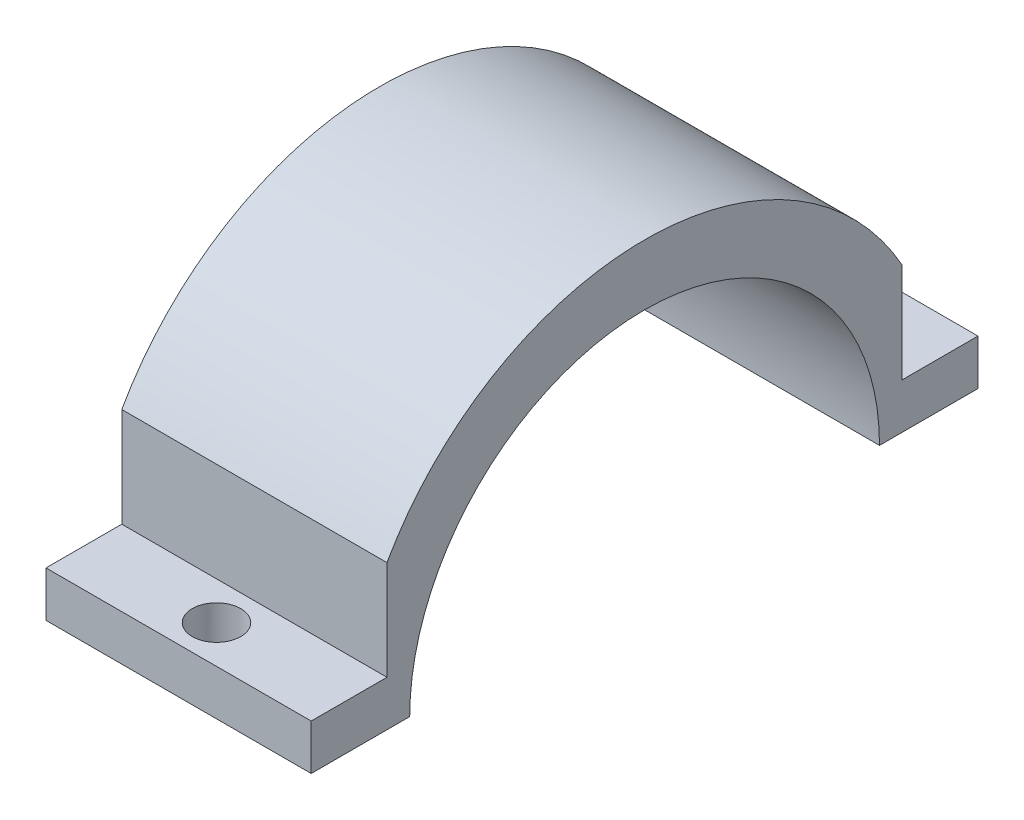
SolidWorks part; units mm, degrees
ref_plane "前视基准面" through (0, 0, 0) normal (0, 0, 1) x (1, 0, 0)
ref_plane "上视基准面" through (0, 0, 0) normal (0, 1, 0) x (1, 0, 0)
ref_plane "右视基准面" through (0, 0, 0) normal (1, 0, 0) x (0, 0, -1)
sketch "草图1" plane through (0, 0, 0) normal (0, 1, 0) x (1, 0, 0)
  line L1 (0, 0) -> (17, 0)
  line L2 (0, 0) -> (0, -40)
  line L3 (0, -40) -> (17, -40)
  line L4 (17, 0) -> (17, -40)
  dimension "D1" = 17
  dimension "D2" = 40
extrude "凸台-拉伸1" add sketch "草图1" along normal blind 50
sketch "草图2" plane through (0, 0, 0) normal (0, -1, 0) x (1, 0, 0)
  line L0 (0, 39) -> (0, 40)
  line L1 (-0.5, 39) -> (17, 39) construction
  line L2 (0, 0) -> (0, 40) construction
  line L3 (0, 40) -> (17, 40)
  line L4 (17, 40) -> (17, 39)
  line L5 (17, 40) -> (17, 0) construction
  line L6 (17, 39) -> (0, 39)
extrude "切除-拉伸1" cut sketch "草图2" against normal through all
sketch "草图4" plane through (0, 0, 0) normal (0, -1, 0) x (1, 0, 0)
  line L2 (-0.5, 0) -> (0, 0)
  line L3 (0, 0) -> (0, 39)
  line L4 (-0.5, 0) -> (-0.5, 39)
  line L5 (-0.5, 39) -> (0, 39)
extrude "凸台-拉伸2" add sketch "草图4" against normal up to vertex (50 mm away) up to point (0, 50, 39)
sketch "草图5" plane through (17, 0, 0) normal (1, 0, 0) x (0, 0, -1)
  circle A0 centre (-22, 4.5) radius 15.5
extrude "切除-拉伸2" cut sketch "草图5" against normal up to vertex (17.5 mm away) up to point (-0.5, 0, 0)
sketch "草图6" plane through (17, 0, 0) normal (1, 0, 0) x (0, 0, -1)
  line L0 (0, 24) -> (0, 3)
  line L2 (-22, 24) -> (-5, 24)
  line L3 (0, 50) -> (0, 0) construction
  line L4 (0, 24) -> (0, 50)
  line L5 (0, 50) -> (-39, 50)
  line L6 (-39, 50) -> (-39, 24)
  line L7 (-39, 50) -> (-39, 0) construction
  line L8 (-39, 24) -> (-22, 24)
  line L9 (0, 0) -> (0, 3)
  line L10 (0, 3) -> (-5, 3)
  line L11 (-5, 3) -> (-5, 24)
  line L12 (0, 24) -> (0, 3)
  line M11 (0, 0) -> (0, 50)
  line M12 (0, 50) -> (-39, 50)
  line M13 (-39, 50) -> (-39, 0)
extrude "切除-拉伸3" cut sketch "草图6" against normal up to vertex (17.5 mm away) contours L11 L10 L8 L2 M11 M12 M13 region at (17, 34.7949, 17.9048) up to point (-0.5, 0, 0)
sketch "草图7" plane through (0, 3, 0) normal (0, 1, 0) x (1, 0, 0)
  line L0 (8.25, -5) -> (8.25, 0)
  line L1 (-0.5, -5) -> (17, -5) construction
  line L2 (-0.5, 0) -> (17, 0) construction
  circle A0 centre (8.25, -2.5) radius 1.6
extrude "切除-拉伸4" cut sketch "草图7" against normal up to vertex (3 mm away) contours L0 A0 | L0 A0 region at (7.5709, 3, 2.5) region at (8.9291, 3, 2.5) up to point (17, 0, 0)
sketch "草图8" plane through (-0.5, 0, 0) normal (-1, 0, 0) x (0, 0, 1)
  line L0 (22, 4.5) -> (5, 4.5)
  line L1 (5, 3) -> (5, 24) construction
  line L2 (22, 4.5) -> (39, 4.5)
  line L3 (39, 24) -> (39, 0) construction
  line L4 (39, 4.5) -> (39, 0)
  line L5 (39, 0) -> (17.2565, -28.4468)
  line L6 (17.2565, -28.4468) -> (-8.6135, 4.5)
  line L7 (-8.6135, 4.5) -> (5, 4.5)
  circle A0 centre (22, 4.5) radius 15.5
  line M2 (5, 24) -> (5, 3)
  line M3 (5, 3) -> (0, 3)
  line M4 (0, 3) -> (0, 0)
  line M5 (0, 0) -> (7.1676, 0)
  arc M6 (7.1676, 0) -> (36.8324, 0) centre (22, 4.5) cw
  line M7 (36.8324, 0) -> (39, 0)
  line M8 (39, 0) -> (39, 24)
extrude "切除-拉伸7" cut sketch "草图8" against normal blind 64 contours A0 L7 L6 L5 M5 M4 M3 M2 M7 | L0 M6 M2 M3 M4 M5 | A0 L2 L0 M6 | L2 M6 M7 M8 region at (-0.5, -2.0784, 22) region at (-0.5, 1.706, 3.6479) region at (-0.5, 2.1051, 38.1283) region at (-0.5, -11.1555, 12.5271)
sketch "草图9" plane through (-0.5, 0, 0) normal (-1, 0, 0) x (0, 0, 1)
  line L0 (5, 4.5) -> (5, 7.5)
  line L1 (5, 4.5) -> (5, 24) construction
  line L2 (5, 7.5) -> (0, 7.5)
  line L3 (0, 7.5) -> (0, 4.5)
  line L4 (0, 4.5) -> (5, 4.5)
  line L5 (39, 4.5) -> (39, 7.5)
  line L6 (39, 24) -> (39, 4.5) construction
  line L7 (39, 7.5) -> (44, 7.5)
  line L8 (44, 7.5) -> (44, 4.5)
  line L9 (44, 4.5) -> (39, 4.5)
extrude "凸台-拉伸3" add sketch "草图9" against normal up to vertex (17.5 mm away) up to point (17, 4.5, 5)
sketch "草图10" plane through (-0.5, 0, 0) normal (-1, 0, 0) x (0, 0, 1)
  line L0 (6.5, 4.5) -> (37.5, 4.5)
  line L1 (5, 14.0525) -> (5, 24)
  line L2 (5, 7.5) -> (5, 24) construction
  line L3 (5, 24) -> (39, 24)
  line L4 (39, 24) -> (39, 14.0525)
  line L5 (39, 24) -> (39, 7.5) construction
  arc A0 (39, 14.0525) -> (5, 14.0525) centre (22, 4.5) ccw
  line M1 (5, 24) -> (5, 7.5)
  line M9 (39, 7.5) -> (39, 24)
  line M10 (39, 24) -> (5, 24)
extrude "切除-拉伸8" cut sketch "草图10" against normal through all and the other way through all contours A0 L3 M1 | A0 M9 M10 region at (-0.5, 21.2146, 34.9963) region at (-0.5, 21.2146, 9.0037)
sketch "草图11" plane through (0, 7.5, 0) normal (0, 1, 0) x (1, 0, 0)
  line L0 (8.25, -5) -> (8.25, 0)
  line L1 (17, -5) -> (-0.5, -5) construction
  line L2 (17, 0) -> (-0.5, 0) construction
  line L3 (8.25, -39) -> (8.25, -44)
  line L4 (17, -39) -> (-0.5, -39) construction
  line L5 (17, -44) -> (-0.5, -44) construction
  circle A0 centre (8.25, -2.5) radius 1.6
  circle A1 centre (8.25, -41.5) radius 1.6
extrude "切除-拉伸9" cut sketch "草图11" against normal blind 64 contours L0 A0 | L0 A0 | L3 A1 | L3 A1 region at (7.5709, 7.5, 2.5) region at (8.9291, 7.5, 2.5) region at (8.9291, 7.5, 41.5) region at (7.5709, 7.5, 41.5)
